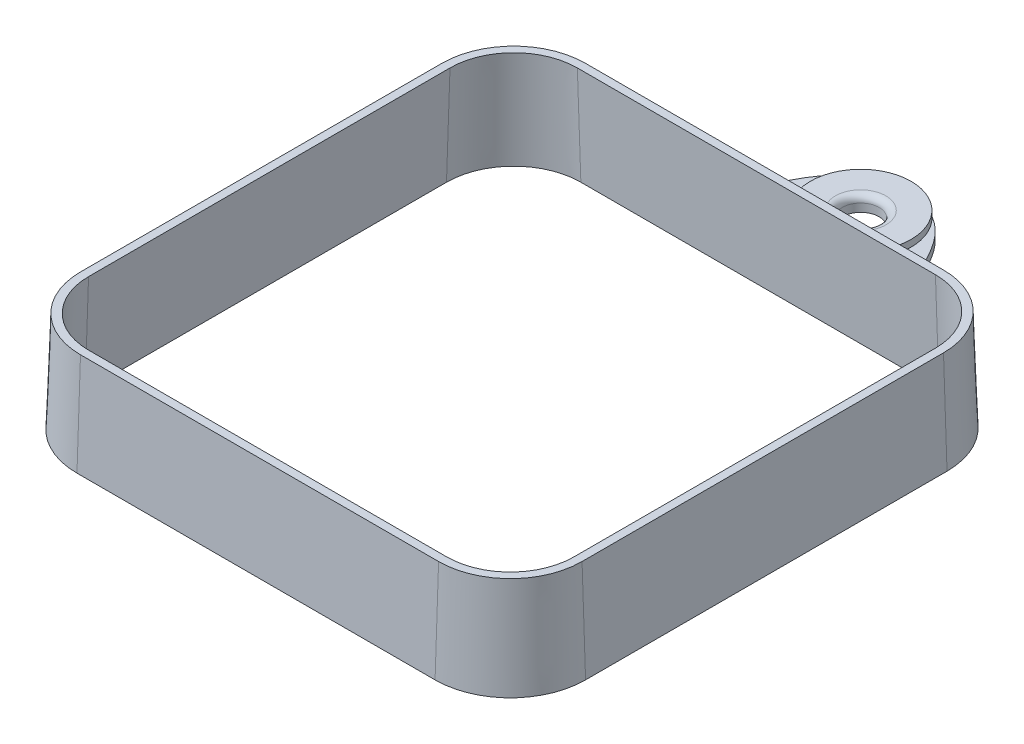
SolidWorks part; units mm, degrees
ref_plane "Front Plane" through (0, 0, 0) normal (0, 0, 1) x (1, 0, 0)
ref_plane "Top Plane" through (0, 0, 0) normal (0, 1, 0) x (1, 0, 0)
ref_plane "Right Plane" through (0, 0, 0) normal (1, 0, 0) x (0, 0, -1)
sketch "Sketch1" plane through (0, 0, 0) normal (0, 1, 0) x (1, 0, 0)
  line L0 (0, 36.9) -> (0, 51.9)
  line L1 (-26.65, -36.9) -> (26.65, -36.9)
  line L2 (-36.65, -26.9) -> (-36.65, 26.9)
  line L3 (-26.65, 36.9) -> (26.65, 36.9)
  line L4 (36.65, -26.9) -> (36.65, 26.9)
  line L5 (-36.65, -36.9) -> (36.65, 36.9) construction
  line L6 (-36.65, 36.9) -> (36.65, -36.9) construction
  arc A0 (-26.65, -36.9) -> (-36.65, -26.9) centre (-26.65, -26.9) cw
  arc A1 (26.65, -36.9) -> (36.65, -26.9) centre (26.65, -26.9) ccw
  arc A2 (36.65, 26.9) -> (26.65, 36.9) centre (26.65, 26.9) ccw
  arc A3 (-36.65, 26.9) -> (-26.65, 36.9) centre (-26.65, 26.9) cw
  circle A4 centre (0, 51.9) radius 2.75
  circle A5 centre (0, 51.9) radius 7.5
  spline S0 degree 3 poles (-5.0383, 57.4557) (-10.199, 54.5143) (-11.6345, 42.5074) (-22.7687, 38.6973) (-26.65, 36.9) knots 0 0 0 0 0.548123 1 1 1 1
  spline S1 degree 3 poles (5.0383, 57.4557) (10.199, 54.5143) (11.6345, 42.5074) (22.7687, 38.6973) (26.65, 36.9) knots 0 0 0 0 0.548123 1 1 1 1
  point P0 (0, 0)
  point P18 (-8.3512, 54.4694)
  point P19 (-12.9587, 44.9663)
  point P26 (-14.6866, 43.8144)
  dimension "D3" = 10
  dimension "D5" = 5.5
  dimension "D6" = 15
  dimension "D1" = 73.3
  dimension "D2" = 73.8
  dimension "D4" = 15
extrude "Boss-Extrude1" add sketch "Sketch1" along normal blind 15 draft 2 contours A3 L2 A0 L1 A1 L4 A2 L3 region at (0, 0, 0)
shell "Shell1" thickness 1.2 removed face at (0, 15, 0) removed face at (0, 0, 0) outward yes
extrude "Boss-Extrude3" add sketch "Sketch1<4>" along normal blind 2.2 separate body contours A5
sketch "Sketch1<4>" plane through (0, 0, 0) normal (0, 1, 0) x (1, 0, 0) same geometry as "Sketch1"
extrude "Boss-Extrude4" add sketch "Sketch1<5>" along normal blind 1.2 contours A5 S0 L3 L0 | S1 A5 L0 L3 | A5 region at (-9.6679, 0, -42.3099) region at (9.668, 0, -42.3095)
sketch "Sketch1<5>" plane through (0, 0, 0) normal (0, 1, 0) x (1, 0, 0) same geometry as "Sketch1"
extrude "Cut-Extrude1" cut sketch "Sketch1<6>" along normal blind 3 contours A4
sketch "Sketch1<6>" plane through (0, 0, 0) normal (0, 1, 0) x (1, 0, 0) same geometry as "Sketch1"
fillet "Fillet1" radius 4 1 edges at (0, 1.2, -38.0588)
fillet "Fillet2" radius 1 1 edges at (0, 2.2, -49.15)
